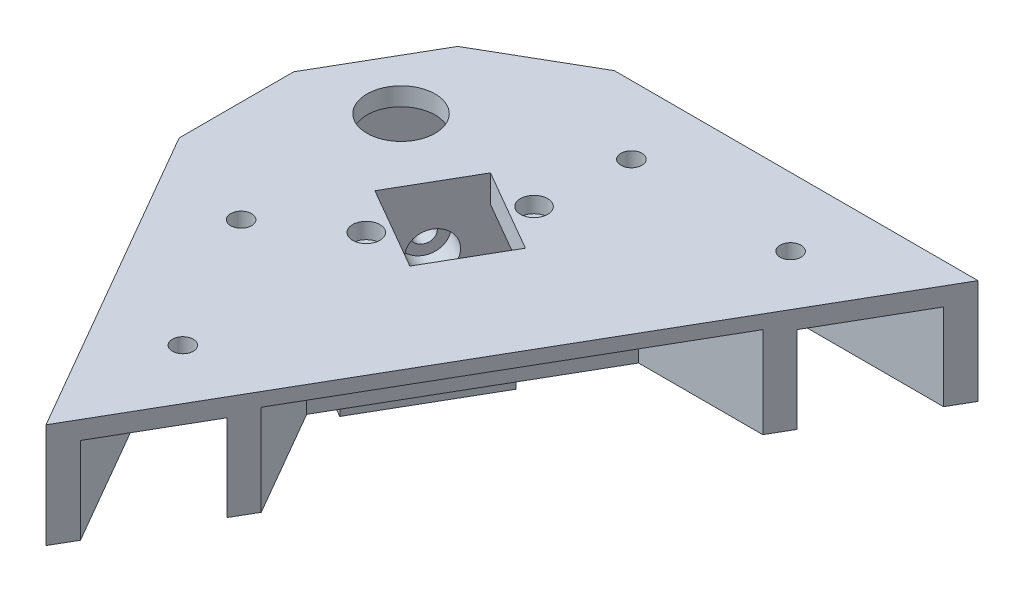
SolidWorks part; units mm, degrees
other "Markup1"
sketch "Sketch26" plane through (25.6218, 0, -129.9038) normal (-0.1134, -0.9932, -0.0259) x (0.9576, -0.1162, 0.2636)
ref_plane "Front Plane" through (0, 0, 0) normal (0, 0, 1) x (1, 0, 0)
ref_plane "Top Plane" through (0, 0, 0) normal (0, 1, 0) x (1, 0, 0)
ref_plane "Right Plane" through (0, 0, 0) normal (1, 0, 0) x (0, 0, -1)
sketch "Sketch1" plane through (0, 0, 0) normal (0, 1, 0) x (1, 0, 0)
  line L0 (0, 0) -> (150, 0)
  line L1 (0, 0) -> (75, 129.9038)
  line L2 (75, 129.9038) -> (150, 0)
  dimension "D1" = 60
  dimension "D2" = 150
  dimension "D3" = 60
extrude "Boss-Extrude1" add sketch "Sketch1" along normal blind 23
sketch "Sketch2" plane through (0, 0, 0) normal (0, 1, 0) x (1, 0, 0)
  line L0 (0, 0) -> (150, 0) construction
  line L1 (74, 5) -> (174, 5) construction
  line L2 (74, 5) -> (74, 25) construction
  line L3 (74, 25) -> (174, 25) construction
  line L4 (174, 5) -> (174, 25) construction
  line L5 (41.3301, 61.5859) -> (91.3301, 148.1884) construction
  line L6 (91.3301, 148.1884) -> (108.6506, 138.1884) construction
  line L7 (108.6506, 138.1884) -> (58.6506, 51.5859) construction
  line L8 (58.6506, 51.5859) -> (41.3301, 61.5859) construction
  line L9 (75, 129.9038) -> (0, 0) construction
  line L10 (108.9238, 138.2616) -> (58.7238, 51.3127)
  line L11 (58.7238, 51.3127) -> (41.0569, 61.5127)
  line L12 (41.0569, 61.5127) -> (91.2569, 148.4616)
  line L13 (91.2569, 148.4616) -> (108.9238, 138.2616)
  line L14 (73.8, 25.2) -> (174.2, 25.2)
  line L15 (174.2, 4.8) -> (174.2, 25.2)
  line L16 (73.8, 4.8) -> (174.2, 4.8)
  line L17 (73.8, 4.8) -> (73.8, 25.2)
  dimension "D1" = 20
  dimension "D2" = 5
  dimension "D3" = 74
  dimension "D4" = 20
  dimension "D5" = 74
  dimension "D6" = 5
  dimension "D7" = 100
  dimension "D8" = 100
  dimension "D9" = 0.2
  dimension "D10" = 0.2
extrude "Cut-Extrude2" cut sketch "Sketch2" along normal blind 19
sketch "Sketch4" plane through (0, 0, 0) normal (0, 1, 0) x (1, 0, 0)
  line L4 (135.4508, 25.2) -> (89.5492, 104.7038) construction
  line L5 (41.1219, 35.2887) -> (0, 0) construction
  line L6 (0, 0) -> (52.9457, 91.7047) construction
  line L7 (68.4424, 27.9682) -> (51.1219, 17.9682) construction
  line L8 (68.4424, 27.9682) -> (58.4424, 45.2887) construction
  line L9 (58.4424, 45.2887) -> (41.1219, 35.2887) construction
  line L10 (51.1219, 17.9682) -> (41.1219, 35.2887) construction
  line L11 (68.4424, 27.9682) -> (41.1219, 35.2887) construction
  line L12 (58.4424, 45.2887) -> (51.1219, 17.9682) construction
  line L13 (58.5156, 45.5619) -> (40.8487, 35.3619)
  line L14 (75, 129.9038) -> (0, 0) construction
  line L15 (0, 0) -> (130.8784, 0) construction
  line L16 (0, 0) -> (150, 0) construction
  line L17 (51.0487, 17.695) -> (40.8487, 35.3619)
  line L18 (68.7156, 27.895) -> (51.0487, 17.695)
  line L19 (68.7156, 27.895) -> (58.5156, 45.5619)
  line L20 (51.1219, 17.9682) -> (0, 0) construction
  point P0 (54.7821, 31.6285)
  dimension "D1" = 20
  dimension "D2" = 20
  dimension "D3" = 21.269
  dimension "D4" = 0.2
  dimension "D5" = 54.1877
  dimension "D6" = 19.365
extrude "Cut-Extrude3" cut sketch "Sketch4" along normal blind 19
ref_plane "Plane1" through (42.4846, 0, -24.5285) normal (0.866, 0, -0.5) x (-0.5, 0, -0.866)
sketch "Sketch22" plane through (0, 0, 0) normal (0, -1, 0) x (1, 0, 0)
  line L0 (79.8892, -26.1478) -> (62.5892, -56.1122)
  line L1 (62.5892, -56.1122) -> (80.7758, -66.6122)
  line L2 (80.7758, -66.6122) -> (98.0758, -36.6478)
  line L3 (98.0758, -36.6478) -> (79.8892, -26.1478)
  line L5 (135.4508, -25.2) -> (89.5492, -104.7038) construction
  dimension "D1" = 82.26
  dimension "D2" = 17.3
  dimension "D3" = 17.3
  dimension "D4" = 21
extrude "Cut-Extrude11" cut sketch "Sketch22" against normal through all both and the other way through all
sketch "Sketch21" plane through (0, 0, 0) normal (0, -1, 0) x (1, 0, 0)
  line L0 (132.6795, -30) -> (105.378, -30)
  line L1 (105.378, -30) -> (78.6697, -76.26)
  line L2 (78.6697, -76.26) -> (92.3205, -99.9038)
  line L3 (92.3205, -99.9038) -> (132.6795, -30)
  line L4 (135.4508, -25.2) -> (89.5492, -104.7038) construction
  line L5 (135.4508, -25.2) -> (73.8, -25.2) construction
  line L7 (58.7238, -51.3127) -> (89.5492, -104.7038) construction
  line L8 (58.7238, -51.3127) -> (89.5492, -104.7038) construction
  line L9 (80.7758, -66.6122) -> (98.0758, -36.6478) construction
  dimension "D1" = 3
  dimension "D2" = 4.8
  dimension "D3" = 4.8
extrude "Cut-Extrude10" cut sketch "Sketch21" against normal offset from surface (20 mm away) 3 up to face at (80.3325, 23, -46.38)
sketch "Sketch38" plane through (0, 19, 0) normal (0, -1, 0) x (1, 0, 0)
  line L0 (49.8904, -56.4127) -> (83.6603, -114.9038) construction
  line L1 (41.0569, -61.5127) -> (58.7238, -51.3127) construction
  line L2 (77.7713, -125.1038) -> (89.5492, -104.7038) construction
  line L3 (73.8, -15) -> (141.3397, -15) construction
  line L4 (73.8, -25.2) -> (73.8, -4.8) construction
  line L5 (135.4508, -25.2) -> (147.2287, -4.8) construction
  line L6 (41.0569, -61.5127) -> (58.7238, -51.3127) construction
  circle A0 centre (88.8, -15) radius 2.3
  circle A1 centre (123.8, -15) radius 2.3
  circle A2 centre (57.3904, -69.4031) radius 2.3
  circle A3 centre (74.8904, -99.7139) radius 2.3
  dimension "D1" = 4.6
  dimension "D2" = 15
  dimension "D3" = 35
  dimension "D4" = 15
  dimension "D5" = 35
extrude "Cut-Extrude24" cut sketch "Sketch38" against normal blind 10
sketch "Sketch39" plane through (0, 23, 0) normal (0, 1, 0) x (1, 0, 0)
  line L0 (62.5892, 56.1122) -> (80.7758, 66.6122)
  line L1 (80.7758, 66.6122) -> (84.7758, 59.684)
  line L2 (80.7758, 66.6122) -> (98.0758, 36.6478) construction
  line L3 (84.7758, 59.684) -> (66.5892, 49.184)
  line L4 (79.8892, 26.1478) -> (62.5892, 56.1122) construction
  line L5 (66.5892, 49.184) -> (62.5892, 56.1122)
  line L6 (98.0758, 36.6478) -> (79.8892, 26.1478)
  line L7 (79.8892, 26.1478) -> (75.8892, 33.076)
  line L8 (75.8892, 33.076) -> (94.0758, 43.576)
  line L9 (94.0758, 43.576) -> (98.0758, 36.6478)
  dimension "D1" = 8
  dimension "D2" = 8
extrude "Boss-Extrude2" add sketch "Sketch39" against normal blind 6
sketch "Sketch40" plane through (0, 17, 0) normal (0, -1, 0) x (1, 0, 0)
  line L0 (88.9825, -31.3978) -> (71.6825, -61.3622) construction
  line L1 (98.0758, -36.6478) -> (79.8892, -26.1478) construction
  line L2 (62.5892, -56.1122) -> (80.7758, -66.6122) construction
  line L3 (80.7758, -66.6122) -> (62.5892, -56.1122) construction
  circle A0 centre (87.0825, -34.6887) radius 1.65
  circle A1 centre (73.5825, -58.0713) radius 1.65
  dimension "D1" = 3.3
  dimension "D2" = 3.3
  dimension "D3" = 3.8
  dimension "D4" = 3.8
extrude "Cut-Extrude25" cut sketch "Sketch40" against normal through all
sketch "Sketch41" plane through (0, 23, 0) normal (0, 1, 0) x (1, 0, 0)
  circle A0 centre (73.5825, 58.0713) radius 3
  circle A1 centre (87.0825, 34.6887) radius 3
  dimension "D1" = 6
extrude "Cut-Extrude26" cut sketch "Sketch41" against normal blind 3.5
ref_plane "Plane3" through (66.2137, 0, -38.2285) normal (-0.866, 0, 0.5) x (0.5, 0, 0.866)
sketch "Sketch45" plane through (63.6156, 0, -36.7285) normal (-0.866, 0, 0.5) x (0.5, 0, 0.866)
  line L0 (-10.2, 9.5) -> (10.2, 9.5) construction
  line L1 (-10.2, 19) -> (-10.2, 0) construction
  line L2 (10.2, 19) -> (10.2, 0) construction
  circle A0 centre (0, 9.5) radius 2.3
  dimension "D1" = 4.6
extrude "Cut-Extrude29" cut sketch "Sketch45" against normal through all
sketch "Sketch47" plane through (0, 19, 0) normal (0, -1, 0) x (1, 0, 0)
  line L0 (59.8821, -22.795) -> (49.6821, -40.4619) construction
  line L1 (51.0487, -17.695) -> (68.7156, -27.895) construction
  line L2 (58.5156, -45.5619) -> (40.8487, -35.3619) construction
  line L3 (45.9487, -26.5285) -> (63.6156, -36.7285) construction
  line L4 (40.8487, -35.3619) -> (51.0487, -17.695) construction
  line L5 (68.7156, -27.895) -> (58.5156, -45.5619) construction
  circle A0 centre (54.7821, -31.6285) radius 7.5
  dimension "D1" = 15
extrude "Cut-Extrude31" cut sketch "Sketch47" against normal blind 10
sketch "Sketch48" plane through (0, 0, 0) normal (0, -1, 0) x (1, 0, 0)
  line L0 (55.4914, 0) -> (27.7457, -48.0569)
  line L1 (0, 0) -> (150, 0) construction
  line L2 (75, -129.9038) -> (0, 0) construction
  line L4 (55.4914, 0) -> (0, 0)
  line L5 (0, 0) -> (27.7457, -48.0569)
  line L6 (40.8487, -35.3619) -> (51.0487, -17.695) construction
  dimension "D1" = 5
extrude "Cut-Extrude32" cut sketch "Sketch48" against normal through all
sketch "Sketch49" plane through (0, 0, 0) normal (0, -1, 0) x (1, 0, 0)
  line L0 (48.7185, -11.7309) -> (75.9117, -27.4309)
  line L1 (27.7457, -48.0569) -> (55.4914, 0) construction
  line L2 (75.9117, -27.4309) -> (61.7117, -52.026)
  line L3 (61.7117, -52.026) -> (34.5185, -36.326)
  line L4 (58.5156, -45.5619) -> (40.8487, -35.3619) construction
  line L5 (51.0487, -17.695) -> (68.7156, -27.895) construction
  line L6 (68.7156, -27.895) -> (58.5156, -45.5619) construction
  line L7 (48.7185, -11.7309) -> (34.5185, -36.326)
  dimension "D1" = 4
  dimension "D2" = 4
  dimension "D3" = 6
extrude "Boss-Extrude3" add sketch "Sketch49" along normal blind 21
sketch "Sketch50" plane through (0, 0, 0) normal (0, 1, 0) x (1, 0, 0)
  line L0 (40.8487, 35.3619) -> (58.5156, 45.5619)
  line L1 (58.5156, 45.5619) -> (68.7156, 27.895)
  line L2 (68.7156, 27.895) -> (51.0487, 17.695)
  line L3 (51.0487, 17.695) -> (40.8487, 35.3619)
extrude "Cut-Extrude33" cut sketch "Sketch50" against normal through all
chamfer "Chamfer6" distance 0.8 angle 85 2 edges at (62.3151, 0, -19.5809) (48.1151, 0, -44.176) first distance on face at (81.7763, 0, -47.2136)
sketch "Sketch51" plane through (92.0239, 0, -53.13) normal (0.866, 0, -0.5) x (-0.5, 0, -0.866)
  circle A0 centre (0, 9.5) radius 4.5
  dimension "D1" = 9
extrude "Cut-Extrude34" cut sketch "Sketch51" against normal offset from surface (29.8031 mm away) 3 up to face at (64.7656, 9.5, -34.7366)
sketch "Sketch52" plane through (68.8117, 0, -39.7285) normal (0.866, 0, -0.5) x (-0.5, 0, -0.866)
  circle A0 centre (0, -10) radius 2.3
  dimension "D1" = 4.6
  dimension "D2" = 10
extrude "Cut-Extrude35" cut sketch "Sketch52" against normal blind 10
sketch "Sketch53" plane through (7.1, 0, 12.2976) normal (0.5, 0, 0.866) x (0.866, 0, -0.5)
  line L0 (79.4569, -21) -> (48.0569, -21) construction
  line L1 (59.4569, -21) -> (79.4569, -21)
  line L2 (59.4569, -21) -> (59.4569, -1)
  line L3 (59.4569, -1) -> (79.4569, -1)
  line L4 (79.4569, -21) -> (79.4569, -1)
  line L5 (79.4569, 0) -> (79.4569, -9.144) construction
  dimension "D1" = 20
  dimension "D2" = 20
extrude "Cut-Extrude36" cut sketch "Sketch53" along normal blind 10
sketch "Sketch54" plane through (7.1, 0, 12.2976) normal (0.5, 0, 0.866) x (0.866, 0, -0.5)
  circle A0 centre (64.5819, -13.4) radius 0.85
  circle A1 centre (74.5819, -13.4) radius 0.85
  dimension "D1" = 1.7
extrude "Cut-Extrude37" cut sketch "Sketch54" against normal blind 10
chamfer "Chamfer7" distance 1 angle 56 1 edges at (67.6077, -1, -21.8139) first distance on face at (61.3259, -3.3813, -18.4276)
chamfer "Chamfer5" distance 14.54 angle 30 1 edges at (55.4914, 11.5, 0) first distance on face at (41.6185, -1.4288, -24.0285)
chamfer "Chamfer4" distance 14.54 angle 30 1 edges at (27.7457, 11.5, -48.0569) first distance on face at (51.3728, 11.5, -88.9804)
mirror "Mirror1" about plane through (0, 0, 0) normal (0, 0, 1) of bodies 150
delete or keep bodies "Body-Delete/Keep 1" type delete bodies bodies 150
